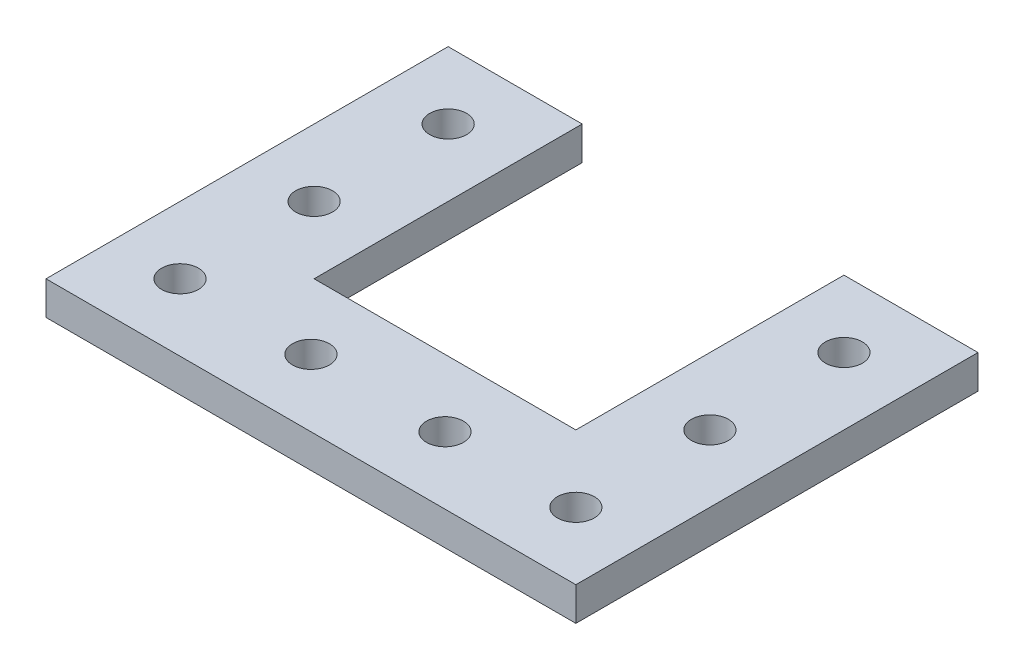
SolidWorks part; units mm, degrees
ref_plane "Front Plane" through (0, 0, 0) normal (0, 0, 1) x (1, 0, 0)
ref_plane "Top Plane" through (0, 0, 0) normal (0, 1, 0) x (1, 0, 0)
ref_plane "Right Plane" through (0, 0, 0) normal (1, 0, 0) x (0, 0, -1)
sketch "Sketch1" plane through (0, 0, 0) normal (0, 1, 0) x (1, 0, 0)
  line L0 (50.2, 0) -> (50.2, 114.9214) construction
  line L1 (0, 0) -> (100.4, 0)
  line L3 (25.4, 25.4) -> (75, 25.4)
  line L5 (100.4, 0) -> (75, 0)
  line L7 (100.4, 76.2) -> (75, 76.2)
  line L8 (75, 25.4) -> (75, 76.2)
  line L9 (25.4, 25.4) -> (25.4, 76.2)
  line L10 (0, 76.2) -> (25.4, 76.2)
  line L12 (0, 0) -> (25.4, 0)
  line L14 (0, 76.2) -> (0, -1.401)
  line L15 (100.4, 0) -> (100.4, 76.2)
  point P1 (50.2, 25.4)
  dimension "D1" = 100.4
  dimension "D2" = 76.2
  dimension "D3" = 25.4
  dimension "D4" = 25.4
extrude "Boss-Extrude1" add sketch "Sketch1" along normal blind 6.35 contours L0 L1 L15 L7 L8 L3 | L1 L0 L3 L9 L10 L14 region at (18.8632, 0, -31.8632) region at (81.5368, 0, -31.8632)
sketch "Sketch2" plane through (0, 6.35, 0) normal (0, 1, 0) x (1, 0, 0)
  line L0 (12.7, 76.2) -> (12.7, 0) construction
  line L1 (0, 76.2) -> (25.4, 76.2) construction
  line L2 (0, 0) -> (100.4, 0) construction
  line L3 (50.2, 25.4) -> (50.2, 0) construction
  line L4 (25.4, 25.4) -> (75, 25.4) construction
  line L5 (12.7, 12.7) -> (87.7, 12.7) construction
  circle A0 centre (12.7, 12.7) radius 3.5
  circle A1 centre (12.7, 38.1) radius 3.5
  circle A2 centre (12.7, 63.5) radius 3.5
  circle A3 centre (87.7, 63.5) radius 3.5
  circle A4 centre (87.7, 38.1) radius 3.5
  circle A5 centre (87.7, 12.7) radius 3.5
  circle A6 centre (37.5, 12.7) radius 3.5
  circle A7 centre (62.9, 12.7) radius 3.5
  point P24 (0, 0)
  point P27 (0, 0)
  dimension "D1" = 7
  dimension "D2" = 12.7
  dimension "D4" = 12.7
  dimension "D5" = 12.7
  dimension "D3" = 3
extrude "Cut-Extrude1" cut sketch "Sketch2" against normal blind 6.35
